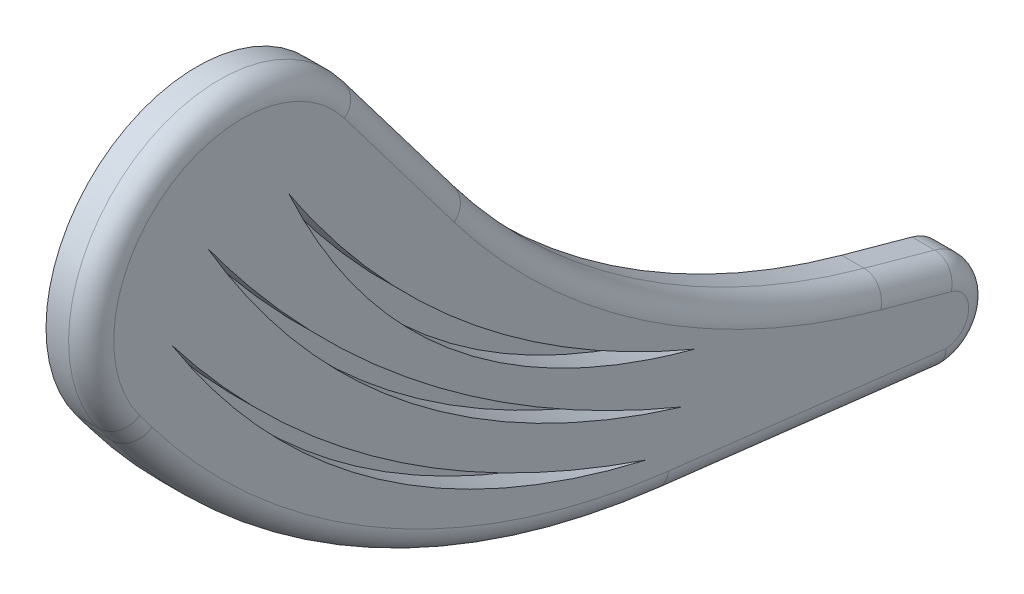
SolidWorks part; units mm, degrees
ref_plane "Front Plane" through (0, 0, 0) normal (0, 0, 1) x (1, 0, 0)
ref_plane "Top Plane" through (0, 0, 0) normal (0, 1, 0) x (1, 0, 0)
ref_plane "Right Plane" through (0, 0, 0) normal (1, 0, 0) x (0, 0, -1)
sketch "Sketch1" plane through (0, 0, 0) normal (1, 0, 0) x (0, 0, -1)
  line L0 (-16.4702, 39.9905) -> (-4.1375, 23.7118)
  line L1 (42.5028, -7.9131) -> (50.4325, -10.1013)
  line L2 (-43.5493, 19.5132) -> (-42.1503, 17.6597)
  line L3 (17.6642, -16.6495) -> (49.0446, -20.3483)
  arc A0 (-16.4702, 39.9905) -> (-43.5493, 19.5132) centre (-30.0007, 29.7398) ccw
  arc A1 (47.8315, -20.2053) -> (50.4325, -10.1013) centre (49.0446, -15.1308) ccw
  arc A2 (17.6642, -16.6495) -> (-42.1503, 17.6597) centre (27.9446, 70.5682) cw
  arc A3 (-4.1375, 23.7118) -> (42.5028, -7.9131) centre (65.8636, 76.7444) ccw
  dimension "D1" = 87.8215
  dimension "D2" = 87.8215
  dimension "D3" = 65.5149
extrude "Boss-Extrude1" add sketch "Sketch1" along normal blind 5.08 contours A3 L0 A0 L2 A2 L3 A1 L1 region at (0, 10.2912, 6.7495)
fillet "Fillet1" radius 2.54 8 edges at (5.08, -9.0072, -46.4677) (5.08, -15.8311, -54.2149) (5.08, -18.4989, -33.3544) (5.08, -5.6111, 15.7512) (5.08, 18.5864, 42.8498) (5.08, 43.2794, 40.2394) (5.08, 31.8511, 10.3039) (5.08, 4.0569, -16.5772)
sketch "Sketch2" plane through (5.08, 0, 0) normal (1, 0, 0) x (0, 0, -1)
  spline S0 degree 2 poles (-37.8914, 26.0453) (-18.8407, -3.8434) (15.5253, -11.809) knots 0 0 0 1 1 1
  spline S1 degree 2 poles (-33.8956, 33.511) (-15.4587, 1.994) (19.521, -8.6545) knots 0 0 0 1 1 1
  spline S2 degree 2 poles (-24.7475, 34.2471) (-7.7443, 8.3304) (20.888, -3.7124) knots 0 0 0 1 1 1
  spline S3 degree 2 poles (-37.8914, 26.0453) (-17.4264, -0.6195) (15.5253, -11.809) knots 0 0 0 1 1 1
  spline S4 degree 2 poles (-33.8956, 33.511) (-13.037, 4.8443) (19.521, -8.6545) knots 0 0 0 1 1 1
  spline S5 degree 2 poles (-24.7475, 34.2471) (-11.2306, 4.8437) (20.888, -3.7124) knots 0 0 0 1 1 1
extrude "Cut-Extrude1" cut sketch "Sketch2" against normal blind 2.54
scale "Scale5" scale about origin uniform scaling yes scale factor 0.8
